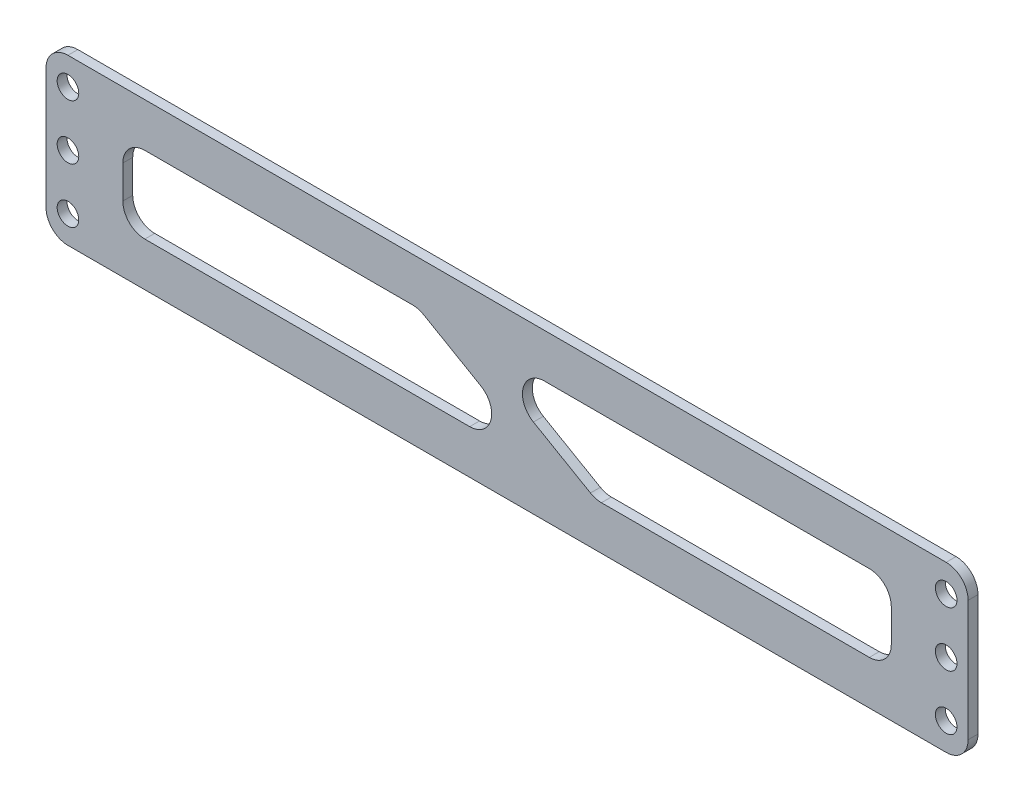
SolidWorks part; units mm, degrees
material "6061 Alloy"
ref_plane "Front Plane" through (0, 0, 0) normal (0, 0, 1) x (1, 0, 0)
ref_plane "Top Plane" through (0, 0, 0) normal (0, 1, 0) x (1, 0, 0)
ref_plane "Right Plane" through (0, 0, 0) normal (1, 0, 0) x (0, 0, -1)
sketch "Sketch1" plane through (0, 0, 0) normal (0, 0, 1) x (1, 0, 0)
  line L1 (-12.7, 774.7) -> (49987.3, 774.7) construction
  line L2 (-7.62, 368.3) -> (210.82, 368.3) construction
  line L3 (-12.7, 1181.1) -> (-12.7, 368.3) construction
  line L4 (-7.62, 755.65) -> (210.82, 755.65)
  line L5 (-12.7, 760.73) -> (-12.7, 788.67)
  line L6 (-7.62, 793.75) -> (210.82, 793.75)
  line L7 (215.9, 760.73) -> (215.9, 788.67)
  line L8 (215.9, 1181.1) -> (215.9, 368.3) construction
  line L9 (17.78, 783.59) -> (79.7609, 783.59)
  line L10 (12.7, 1181.1) -> (12.7, 368.3) construction
  line L11 (190.5, 1181.1) -> (190.5, 368.3) construction
  line L12 (190.5, 778.51) -> (190.5, 770.89)
  line L13 (185.42, 765.81) -> (123.4391, 765.81)
  line L14 (12.7, 770.89) -> (12.7, 778.51)
  line L15 (82.3009, 782.9094) -> (95.4991, 775.2894)
  line L16 (107.7009, 774.1106) -> (120.8991, 766.4906)
  line L17 (81.1221, 783.59) -> (81.1221, -49216.41) construction
  line L18 (122.0779, 765.81) -> (122.0779, 50765.81) construction
  line L19 (101.6, 765.81) -> (101.6, 50765.81) construction
  line L20 (110.2409, 783.59) -> (185.42, 783.59)
  line L21 (92.9591, 765.81) -> (17.78, 765.81)
  arc A0 (210.82, 793.75) -> (215.9, 788.67) centre (210.82, 788.67) cw
  arc A1 (210.82, 755.65) -> (215.9, 760.73) centre (210.82, 760.73) ccw
  arc A2 (-12.7, 788.67) -> (-7.62, 793.75) centre (-7.62, 788.67) cw
  arc A3 (-7.62, 755.65) -> (-12.7, 760.73) centre (-7.62, 760.73) cw
  circle A4 centre (0, 762) radius 2.5
  circle A5 centre (0, 774.7) radius 2.5
  circle A6 centre (0, 787.4) radius 2.5
  circle A7 centre (203.2, 762) radius 2.5
  circle A8 centre (203.2, 774.7) radius 2.5
  circle A9 centre (203.2, 787.4) radius 2.5
  arc A10 (185.42, 783.59) -> (190.5, 778.51) centre (185.42, 778.51) cw
  arc A11 (190.5, 770.89) -> (185.42, 765.81) centre (185.42, 770.89) cw
  arc A12 (17.78, 765.81) -> (12.7, 770.89) centre (17.78, 770.89) cw
  arc A13 (17.78, 783.59) -> (12.7, 778.51) centre (17.78, 778.51) ccw
  arc A14 (120.8991, 766.4906) -> (123.4391, 765.81) centre (123.4391, 770.89) ccw
  arc A15 (107.7009, 774.1106) -> (110.2409, 783.59) centre (110.2409, 778.51) cw
  arc A16 (82.3009, 782.9094) -> (79.7609, 783.59) centre (79.7609, 778.51) ccw
  arc A17 (95.4991, 775.2894) -> (92.9591, 765.81) centre (92.9591, 770.89) cw
  point P14 (215.9, 793.75)
  point P17 (215.9, 755.65)
  point P22 (-12.7, 755.65)
  point P55 (190.5, 783.59)
  point P58 (190.5, 765.81)
  point P61 (12.7, 765.81)
  point P64 (12.7, 783.59)
  point P73 (122.0779, 765.81)
  point P76 (91.2821, 783.59)
  point P79 (81.1221, 783.59)
  point P82 (111.9179, 765.81)
  dimension "D4" = 5.08
  dimension "D7" = 5.08
  dimension "D12" = 5.08
  dimension "D1" = 406.4
  dimension "D2" = 38.1
  dimension "D3" = 19.05
  dimension "D5" = 10.16
  dimension "D6" = 10.16
  dimension "D8" = 5.08
  dimension "D9" = 30
  dimension "D10" = 20.4779
  dimension "D11" = 88.9
extrude "Boss-Extrude1" add sketch "Sketch1" along normal blind 2.286
sketch "Sketch2" [suppressed] plane through (0, 0, 0) normal (0, 0, 1) x (1, 0, 0)
  circle A0 centre (27.1191, 775.0388) radius 2.54
  circle A1 centre (68.5634, 775.0388) radius 2.54
  circle A2 centre (133.0475, 775.0388) radius 2.54
  circle A3 centre (171.352, 775.0388) radius 2.54
  dimension "D1" = 5.08
sketch "Sketch3" plane through (0, 0, 0) normal (0, 0, -1) x (-1, 0, 0)
  line L0 (7.62, 755.65) -> (-210.82, 755.65) construction
  line L1 (-208.28, 755.65) -> (5.08, 755.65)
  line L2 (-208.28, 755.65) -> (-208.28, 793.75)
  line L3 (-208.28, 793.75) -> (5.08, 793.75)
  line L4 (5.08, 755.65) -> (5.08, 793.75)
  line L5 (-210.82, 793.75) -> (7.62, 793.75) construction
  line L6 (-215.9, 760.73) -> (-215.9, 788.67) construction
  line L7 (12.7, 788.67) -> (12.7, 760.73) construction
  line L12 (-215.9, 788.67) -> (-215.9, 760.73)
  line L13 (-210.82, 755.65) -> (7.62, 755.65)
  line L14 (12.7, 760.73) -> (12.7, 788.67)
  line L15 (7.62, 793.75) -> (-210.82, 793.75)
  line L16 (-215.9, 788.67) -> (-215.9, 760.73)
  line L17 (-210.82, 755.65) -> (7.62, 755.65)
  line L18 (12.7, 760.73) -> (12.7, 788.67)
  line L19 (7.62, 793.75) -> (-210.82, 793.75)
  arc A4 (-210.82, 793.75) -> (-215.9, 788.67) centre (-210.82, 788.67) ccw
  arc A5 (-215.9, 760.73) -> (-210.82, 755.65) centre (-210.82, 760.73) ccw
  arc A6 (7.62, 755.65) -> (12.7, 760.73) centre (7.62, 760.73) ccw
  arc A7 (12.7, 788.67) -> (7.62, 793.75) centre (7.62, 788.67) ccw
  arc A8 (-210.82, 793.75) -> (-215.9, 788.67) centre (-210.82, 788.67) ccw
  arc A9 (-215.9, 760.73) -> (-210.82, 755.65) centre (-210.82, 760.73) ccw
  arc A10 (7.62, 755.65) -> (12.7, 760.73) centre (7.62, 760.73) ccw
  arc A11 (12.7, 788.67) -> (7.62, 793.75) centre (7.62, 788.67) ccw
  arc M14 (-210.82, 793.75) -> (-215.9, 788.67) centre (-210.82, 788.67) ccw
  line M15 (-215.9, 788.67) -> (-215.9, 760.73)
  arc M16 (-215.9, 760.73) -> (-210.82, 755.65) centre (-210.82, 760.73) ccw
  line M17 (-210.82, 755.65) -> (7.62, 755.65)
  arc M18 (7.62, 755.65) -> (12.7, 760.73) centre (7.62, 760.73) ccw
  line M19 (12.7, 760.73) -> (12.7, 788.67)
  arc M20 (12.7, 788.67) -> (7.62, 793.75) centre (7.62, 788.67) ccw
  line M21 (7.62, 793.75) -> (-210.82, 793.75)
  dimension "D1" = 7.62
  dimension "D2" = 7.62
  dimension "D3" = 0
extrude "Cut-Extrude1" cut sketch "Sketch3" against normal through all contours L2 M17 M21 M14 M15 M16 | L4 M17 M18 M19 M20 M21 region at (211.9839, 774.7, 0) region at (-8.7839, 774.7, 0)
fillet "Fillet1" radius 5.08 4 edges at (-5.08, 755.65, 1.143) (-5.08, 793.75, 1.143) (208.28, 755.65, 1.143) (208.28, 793.75, 1.143)
